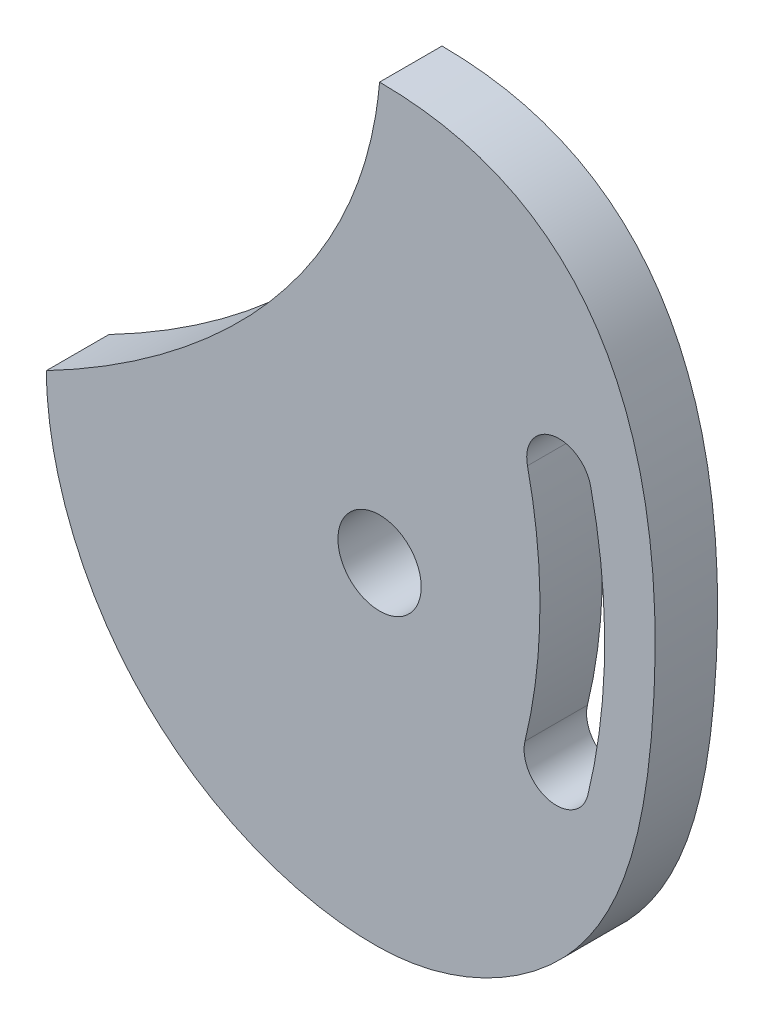
SolidWorks part; units mm, degrees
material "ASTM A36 Steel"
ref_plane "Front Plane" through (0, 0, 0) normal (0, 0, 1) x (1, 0, 0)
ref_plane "Top Plane" through (0, 0, 0) normal (0, 1, 0) x (1, 0, 0)
ref_plane "Right Plane" through (0, 0, 0) normal (1, 0, 0) x (0, 0, -1)
other "Center of Mass"
sketch "Sketch2" plane through (0, 0, 0) normal (0, 0, 1) x (1, 0, 0)
  line L0 (0, -127) -> (0, 127) construction
  line L1 (-127, 0) -> (127, 0) construction
  circle A0 centre (0, 0) radius 127 construction
  circle A1 centre (0, 0) radius 101.6 construction
  circle A2 centre (0, 0) radius 12.7
  spline S0 degree 3 poles (0, 127) (75.3234, 126.7783) (93.5228, 28.6506) (71.2661, -74.324) (20.4014, -101.8398) (-31.3061, -101.6054) (-84.126, -73.3502) (-101.5709, -21.9924) (-101.6, 0) knots 0 0 0 0 0.362447 0.534243 0.652639 0.684562 0.85347 1 1 1 1
  spline S1 degree 3 poles (-101.6, 0) (-52.9034, 25.2324) (-5.0652, 68.8738) (0, 127) knots 0 0 0 0 1 1 1 1
  point P15 (83.2552, 0)
  point P17 (70.8233, 87.3927)
  dimension "D1" = 254
  dimension "D2" = 203.2
  dimension "D3" = 25.4
extrude "Boss-Extrude2" add sketch "Sketch2" along normal blind 19.05 contours S1 S0
sketch "Sketch3" plane through (0, 0, 19.05) normal (0, 0, 1) x (1, 0, 0)
  circle A0 centre (0, 0) radius 12.7
  dimension "D1" = 25.4
extrude "Cut-Extrude1" cut sketch "Sketch3" against normal blind 19.05 contours A0
sketch "Sketch5" plane through (0, 0, 19.05) normal (0, 0, 1) x (1, 0, 0)
  arc A0 (53.9325, -27.2249) -> (54.7349, 50.3407) centre (-112.974, 13.2887) ccw construction
  arc A1 (63.5179, -29.5516) -> (64.3664, 52.4686) centre (-112.974, 13.2887) ccw
  arc A2 (44.3471, -24.8983) -> (45.1035, 48.2128) centre (-112.974, 13.2887) ccw
  arc A3 (44.3471, -24.8983) -> (63.5179, -29.5516) centre (53.9325, -27.2249) ccw
  arc A4 (64.3664, 52.4686) -> (45.1035, 48.2128) centre (54.7349, 50.3407) ccw
  point P3 (58.7699, 11.512)
  point P8 (60.829, 35.9587)
  point P9 (65.948, 21.5767)
  point P10 (54.4912, -4.2622)
  point P11 (-115.8992, 23.5268)
  point P12 (-107.6112, 20.3578)
  point P13 (-110.0489, 20.3578)
  point P14 (53.5161, 61.31)
  point P15 (-111.2677, 17.1889)
  point P16 (56.4413, -23.5195)
  point P17 (0, 0)
  point P18 (0, 0)
  point P19 (0, 0)
  point P20 (0, 0)
  point P21 (0, 0)
  point P22 (0, 0)
  point P23 (0, 0)
  point P24 (0, 0)
  point P25 (0, 0)
  point P26 (0, 0)
  point P27 (0, 0)
  point P28 (54.7349, 50.3407)
extrude "Cut-Extrude2" cut sketch "Sketch5" against normal blind 19.05 contours A2 A4 A1 A3
